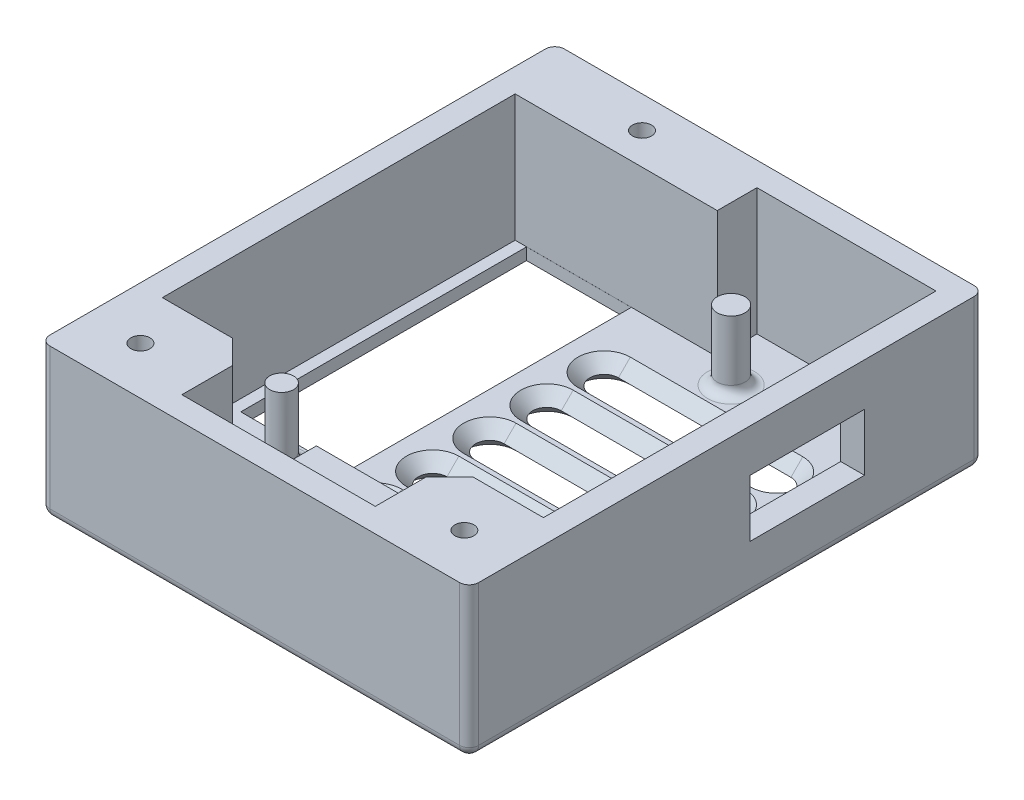
SolidWorks part; units mm, degrees
ref_plane "Front Plane" through (0, 0, 0) normal (0, 0, 1) x (1, 0, 0)
ref_plane "Top Plane" through (0, 0, 0) normal (0, 1, 0) x (1, 0, 0)
ref_plane "Right Plane" through (0, 0, 0) normal (1, 0, 0) x (0, 0, -1)
sketch "Sketch1" plane through (0, 0, 0) normal (0, 1, 0) x (1, 0, 0)
  line L1 (-20, 24.5) -> (20, 24.5)
  line L2 (-20, 24.5) -> (-20, -24.5)
  line L3 (-20, -24.5) -> (20, -24.5)
  line L4 (20, 24.5) -> (20, -24.5)
  line L5 (22.5, -27) -> (-22.5, -27)
  line L6 (22.5, -27) -> (22.5, 27)
  line L7 (22.5, 27) -> (-22.5, 27)
  line L8 (-22.5, -27) -> (-22.5, 27)
  line L9 (22.5, -27) -> (-22.5, 27) construction
  line L10 (22.5, 27) -> (-22.5, -27) construction
  point P4 (0, 0)
  dimension "D1" = 40
  dimension "D2" = 49
  dimension "D3" = 20
  dimension "D4" = 24.5
  dimension "D5" = 45
  dimension "D6" = 54
extrude "Boss-Extrude1" add sketch "Sketch1" along normal blind 13.3
sketch "Sketch3" plane through (0, 0, 0) normal (0, -1, 0) x (1, 0, 0)
  line L1 (-22.5, 27) -> (22.5, 27)
  line L2 (-22.5, 27) -> (-22.5, -27)
  line L3 (-22.5, -27) -> (22.5, -27)
  line L4 (22.5, 27) -> (22.5, -27)
extrude "Boss-Extrude2" add sketch "Sketch3" along normal blind 2.5
sketch "Sketch4" plane through (0, 0, 0) normal (0, 1, 0) x (1, 0, 0)
  line L0 (-12.65, -16.7) -> (-10.15, -19.2)
  line L1 (-20, -24.5) -> (-10.15, -24.5)
  line L2 (-20, -24.5) -> (-20, -16.7)
  line L3 (-20, -16.7) -> (-12.65, -16.7)
  line L4 (-10.15, -24.5) -> (-10.15, -19.2)
  line L5 (12.65, -16.7) -> (10.15, -19.2)
  line L6 (20, -24.5) -> (10.15, -24.5)
  line L7 (20, -24.5) -> (20, -16.7)
  line L8 (20, -16.7) -> (12.65, -16.7)
  line L9 (10.15, -24.5) -> (10.15, -19.2)
  point P1 (-10.15, -16.7)
  point P8 (10.15, -16.7)
  dimension "D1" = 9.85
  dimension "D2" = 7.8
  dimension "D3" = 9.85
  dimension "D4" = 7.8
extrude "Boss-Extrude4" add sketch "Sketch4" along direction (0, 1, 0) on the side of the normal through all
sketch "Sketch5" plane through (0, -2.5, 0) normal (0, -1, 0) x (1, 0, 0)
  line L0 (-22.5, 27) -> (-22.5, -27) construction
  line L1 (-18.8, -20.33) -> (-7.8, -20.33)
  line L2 (-18.8, -20.33) -> (-18.8, 9.67)
  line L3 (-18.8, 9.67) -> (-7.8, 9.67)
  line L4 (-7.8, -20.33) -> (-7.8, 9.67)
  line L5 (-22.5, -27) -> (22.5, -27) construction
  dimension "D1" = 3.7
  dimension "D2" = 11
  dimension "D3" = 30
  dimension "D4" = 6.67
extrude "Cut-Extrude1" cut sketch "Sketch5" against normal blind 5
sketch "Sketch6" plane through (22.5, 0, 0) normal (1, 0, 0) x (0, 0, -1)
  line L0 (27, 13.3) -> (27, -2.5) construction
  line L1 (2.5, 8.8) -> (14.5, 8.8)
  line L2 (2.5, 8.8) -> (2.5, 2.8)
  line L3 (2.5, 2.8) -> (14.5, 2.8)
  line L4 (14.5, 8.8) -> (14.5, 2.8)
  line L5 (-27, 13.3) -> (27, 13.3) construction
  dimension "D1" = 6
  dimension "D2" = 12
  dimension "D3" = 12.5
  dimension "D4" = 4.5
extrude "Cut-Extrude2" cut sketch "Sketch6" against normal blind 5
sketch "Sketch7" plane through (0, 0, 0) normal (0, 1, 0) x (1, 0, 0)
  line L0 (-20, 24.5) -> (-20, -16.7) construction
  line L1 (4.4394, -16.093) -> (-4.4394, -16.093)
  line L2 (4.4394, -16.093) -> (4.4394, -21.2261)
  line L3 (4.4394, -21.2261) -> (-4.4394, -21.2261)
  line L4 (-4.4394, -16.093) -> (-4.4394, -21.2261)
  line L5 (4.4394, -16.093) -> (-4.4394, -21.2261) construction
  line L6 (4.4394, -21.2261) -> (-4.4394, -16.093) construction
  line L7 (20, 24.5) -> (-20, 24.5) construction
  line L8 (22.5, -27) -> (22.5, 27) construction
  circle A0 centre (4.5, 18.5) radius 1.4567
  circle A1 centre (-12, -12.183) radius 1.2475
  point P0 (0, -18.6595)
  dimension "D1" = 6
  dimension "D2" = 8
  dimension "D3" = 18
extrude "Boss-Extrude5" add sketch "Sketch7" along normal blind 7.3
fillet "Fillet1" radius 1 8 edges at (0, -2.5, -27) (-22.5, -2.5, 0) (-22.5, 5.4, -27) (22.5, -2.5, 0) (22.5, 5.4, -27) (-22.5, 5.4, 27) (0, -2.5, 27) (22.5, 5.4, 27)
sketch "Sketch8" plane through (0, 0, 0) normal (0, 1, 0) x (1, 0, 0)
  line L0 (-3.3296, 13) -> (14.775, 13) construction
  line L1 (-3.3296, 14.5) -> (14.775, 14.5)
  line L2 (-3.3296, 11.5) -> (14.775, 11.5)
  line L3 (-3.3296, 7) -> (14.775, 7) construction
  line L4 (-3.3296, 8.5) -> (14.775, 8.5)
  line L5 (-3.3296, 5.5) -> (14.775, 5.5)
  line L6 (-3.3296, 1) -> (14.775, 1) construction
  line L7 (-3.3296, 2.5) -> (14.775, 2.5)
  line L8 (-3.3296, -0.5) -> (14.775, -0.5)
  line L9 (-3.3296, -5) -> (14.775, -5) construction
  line L10 (-3.3296, -3.5) -> (14.775, -3.5)
  line L11 (-3.3296, -6.5) -> (14.775, -6.5)
  line L12 (-3.3296, -11) -> (14.775, -11) construction
  line L13 (-3.3296, -9.5) -> (14.775, -9.5)
  line L14 (-3.3296, -12.5) -> (14.775, -12.5)
  line L15 (20, 24.5) -> (-20, 24.5) construction
  arc A0 (-3.3296, 14.5) -> (-3.3296, 11.5) centre (-3.3296, 13) ccw
  arc A1 (14.775, 11.5) -> (14.775, 14.5) centre (14.775, 13) ccw
  arc A2 (-3.3296, 8.5) -> (-3.3296, 5.5) centre (-3.3296, 7) ccw
  arc A3 (14.775, 5.5) -> (14.775, 8.5) centre (14.775, 7) ccw
  arc A4 (-3.3296, 2.5) -> (-3.3296, -0.5) centre (-3.3296, 1) ccw
  arc A5 (14.775, -0.5) -> (14.775, 2.5) centre (14.775, 1) ccw
  arc A6 (-3.3296, -3.5) -> (-3.3296, -6.5) centre (-3.3296, -5) ccw
  arc A7 (14.775, -6.5) -> (14.775, -3.5) centre (14.775, -5) ccw
  arc A8 (-3.3296, -9.5) -> (-3.3296, -12.5) centre (-3.3296, -11) ccw
  arc A9 (14.775, -12.5) -> (14.775, -9.5) centre (14.775, -11) ccw
  point P2 (5.7227, 13)
  point P7 (5.7227, 7)
  point P14 (5.7227, 1)
  point P21 (5.7227, -5)
  point P28 (5.7227, -11)
  dimension "D1" = 6
  dimension "D2" = 6
  dimension "D3" = 6
  dimension "D4" = 6
  dimension "D6" = 3
  dimension "D7" = 3
  dimension "D9" = 3
  dimension "D10" = 10
extrude "Cut-Extrude3" cut sketch "Sketch8" against normal blind 7.3
fillet "Fillet2" radius 1 6 edges at (4.5, 0, -19.9567) (-12, 0, 10.9356) (0, 0, 21.2261) (4.4394, 0, 18.6595) (0, 0, 16.093) (-4.4394, 0, 18.6595)
chamfer "Chamfer2" distance 1.25 angle 45 20 edges at (5.7227, -2.5, -14.5) (16.275, -2.5, -13) (-4.8296, -2.5, -13) (5.7227, -2.5, -11.5) (5.7227, -2.5, -8.5) (16.275, -2.5, -7) (-4.8296, -2.5, -7) (5.7227, -2.5, -5.5) (5.7227, -2.5, -2.5) (16.275, -2.5, -1) (-4.8296, -2.5, -1) (5.7227, -2.5, 0.5) (5.7227, -2.5, 3.5) (16.275, -2.5, 5) (-4.8296, -2.5, 5) (5.7227, -2.5, 6.5) (5.7227, -2.5, 9.5) (16.275, -2.5, 11) (-4.8296, -2.5, 11) (5.7227, -2.5, 12.5)
chamfer "Chamfer3" distance 1.25 angle 45 20 edges at (5.7227, 0, 12.5) (16.275, 0, 11) (-4.8296, 0, 11) (5.7227, 0, 9.5) (5.7227, 0, 6.5) (16.275, 0, 5) (-4.8296, 0, 5) (5.7227, 0, 3.5) (5.7227, 0, 0.5) (16.275, 0, -1) (-4.8296, 0, -1) (5.7227, 0, -2.5) (5.7227, 0, -5.5) (16.275, 0, -7) (-4.8296, 0, -7) (5.7227, 0, -8.5) (5.7227, 0, -11.5) (16.275, 0, -13) (-4.8296, 0, -13) (5.7227, 0, -14.5)
chamfer "Chamfer4" distance 1.25 angle 45 4 edges at (-13.3, -2.5, -20.33) (-7.8, -2.5, -5.33) (-13.3, -2.5, 9.67) (-18.8, -2.5, -5.33)
sketch "Sketch9" plane through (0, 0, 0) normal (0, 1, 0) x (1, 0, 0)
  line L1 (-20, 24.5) -> (1.2105, 24.5)
  line L2 (-20, 24.5) -> (-20, 20.3348)
  line L3 (-20, 20.3348) -> (1.2105, 20.3348)
  line L4 (1.2105, 24.5) -> (1.2105, 20.3348)
extrude "Boss-Extrude6" add sketch "Sketch9" along normal through all
sketch "Sketch10" plane through (0, 13.3, 0) normal (0, 1, 0) x (1, 0, 0)
  line L0 (21.5, 27) -> (-21.5, 27) construction
  line L1 (-21.5, -27) -> (21.5, -27) construction
  line L2 (22.5, -26) -> (22.5, 26) construction
  line L3 (-22.5, 26) -> (-22.5, -26) construction
  circle A0 centre (-10.0184, 23.665) radius 1
  circle A1 centre (-17, -22) radius 1
  circle A2 centre (17, -22) radius 1
  dimension "D1" = 2
  dimension "D2" = 3.335
  dimension "D3" = 2
  dimension "D4" = 2
  dimension "D5" = 5
  dimension "D6" = 5
  dimension "D7" = 5.5
  dimension "D8" = 5.5
extrude "Cut-Extrude4" cut sketch "Sketch10" against normal blind 7.3
sketch "Sketch11" plane through (0, 0, -27) normal (0, 0, -1) x (-1, 0, 0)
  line L0 (21.5, -2.5) -> (-21.5, -2.5) construction
  line L1 (-22.5, -1.5) -> (-22.5, 13.3) construction
  circle A0 centre (-12.75, 3.25) radius 1.25
  dimension "D3" = 2.5
  dimension "D1" = 7
  dimension "D2" = 9.75
extrude "Cut-Extrude5" cut sketch "Sketch11" against normal blind 10
equation "\"D5@Sketch1\"=\"D1@Sketch1\"+5"
equation "\"D6@Sketch1\"=\"D2@Sketch1\"+5"
equation "\"D3@Sketch4\"=\"D1@Sketch4\""
equation "\"D4@Sketch4\"=\"D2@Sketch4\""
equation "\"D6@Sketch8\"=\"D5@Sketch8\""
equation "\"D7@Sketch8\"=\"D6@Sketch8\""
equation "\"D8@Sketch8\"=\"D6@Sketch8\""
equation "\"D9@Sketch8\"=\"D8@Sketch8\""
